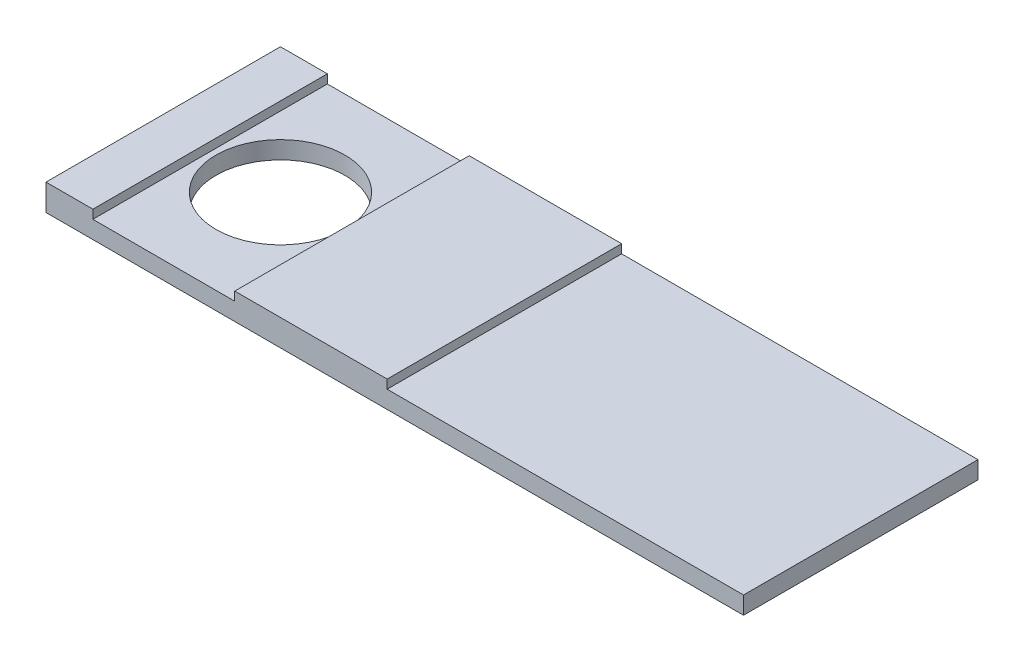
SolidWorks part; units mm, degrees
ref_plane "Front Plane" through (0, 0, 0) normal (0, 0, 1) x (1, 0, 0)
ref_plane "Top Plane" through (0, 0, 0) normal (0, 1, 0) x (1, 0, 0)
ref_plane "Right Plane" through (0, 0, 0) normal (1, 0, 0) x (0, 0, -1)
sketch "Sketch1" plane through (0, 0, 0) normal (0, 1, 0) x (1, 0, 0)
  line L1 (-59.5, -20) -> (59.5, -20)
  line L2 (-59.5, -20) -> (-59.5, 20)
  line L3 (-59.5, 20) -> (59.5, 20)
  line L4 (59.5, -20) -> (59.5, 20)
  line L5 (-59.5, -20) -> (59.5, 20) construction
  line L6 (-59.5, 20) -> (59.5, -20) construction
  circle A0 centre (-39.5, 0) radius 11
  point P0 (0, 0)
  dimension "D5" = 22
  dimension "D1" = 119
  dimension "D2" = 40
  dimension "D3" = 20
  dimension "D4" = 20
extrude "Boss-Extrude1" add sketch "Sketch1" along normal blind 3
sketch "Sketch2" plane through (0, 3, 0) normal (0, 1, 0) x (1, 0, 0)
  line L0 (59.5, 20) -> (-59.5, 20) construction
  line L1 (-27.3, 20) -> (-1.3, 20)
  line L2 (-27.3, 20) -> (-27.3, -20)
  line L3 (-27.3, -20) -> (-1.3, -20)
  line L4 (-1.3, 20) -> (-1.3, -20)
  line L5 (-59.5, -20) -> (59.5, -20) construction
  line L7 (-59.5, 20) -> (-51.5, 20)
  line L8 (-59.5, 20) -> (-59.5, -20)
  line L9 (-59.5, -20) -> (-51.5, -20)
  line L10 (-51.5, 20) -> (-51.5, -20)
  dimension "D1" = 26
  dimension "D2" = 8
  dimension "D4" = 58.2
extrude "Boss-Extrude2" add sketch "Sketch2" along normal blind 1.5
